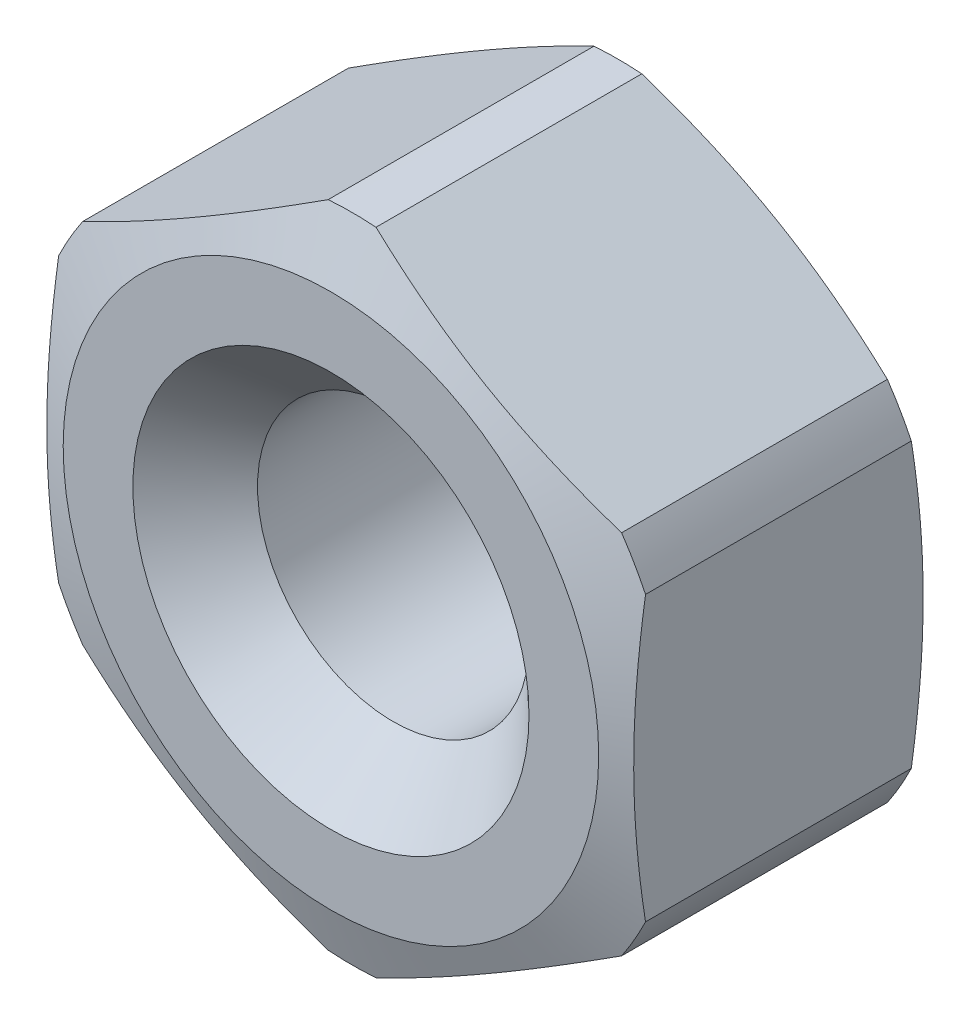
SolidWorks part; units mm, degrees
material "AISI 1020"
ref_plane "Спереди" through (0, 0, 0) normal (0, 0, 1) x (1, 0, 0)
ref_plane "Сверху" through (0, 0, 0) normal (0, 1, 0) x (1, 0, 0)
ref_plane "Справа" through (0, 0, 0) normal (1, 0, 0) x (0, 0, -1)
sketch "Эскиз1" plane through (0, 0, 0) normal (1, 0, 0) x (0, 0, -1)
  line L0 (-152.7402, 0) -> (7484.2692, 0) construction
  line L1 (-2.501, 3.701) -> (2.501, 3.701)
  line L5 (3.6231, 8.885) -> (-3.6231, 8.885)
  line L6 (-3.6231, 8.885) -> (-4.2, 7.3)
  line L7 (-4.2, 7.3) -> (-4.2, 5.4)
  line L8 (-4.2, 5.4) -> (-2.501, 3.701)
  line L9 (0, -152.7402) -> (0, 7484.2692) construction
  line L10 (0, 5) -> (0, -5) construction
  line L11 (-0.75, 5) -> (0.75, 5) construction
  line L12 (0.75, 5) -> (0, 3.701) construction
  line L13 (0, 3.701) -> (-0.75, 5) construction
  line L14 (3.6231, 8.885) -> (4.2, 7.3)
  line L15 (4.2, 7.3) -> (4.2, 5.4)
  line L16 (4.2, 5.4) -> (2.501, 3.701)
  point P8 (0, 0)
  point P16 (0, 5)
  point P20 (0, 8.885)
  point P23 (0, 3.701)
  dimension "D1" = 20
  dimension "_e" = 17.77
  dimension "_dw" = 14.6
  dimension "D2" = 45
  dimension "_da" = 10.8
  dimension "_D" = 10
  dimension "_pa" = 1.5
  dimension "_m" = 8.4
revolve "Повернуть1" add sketch "Эскиз1" angle 360 about L0
sketch "Эскиз2" plane through (0, 0, 4.2) normal (0, 0, 1) x (1, 0, 0)
  line L1 (0, -9.2376) -> (8, -4.6188)
  line L2 (8, -4.6188) -> (8, 4.6188)
  line L3 (8, 4.6188) -> (0, 9.2376)
  line L4 (0, 9.2376) -> (-8, 4.6188)
  line L5 (-8, 4.6188) -> (-8, -4.6188)
  line L6 (-8, -4.6188) -> (0, -9.2376)
  circle A0 centre (0, 0) radius 8 construction
  dimension "_S" = 16
extrude "Вырез-Вытянуть1" cut sketch "Эскиз2" against normal through all flip side to cut
